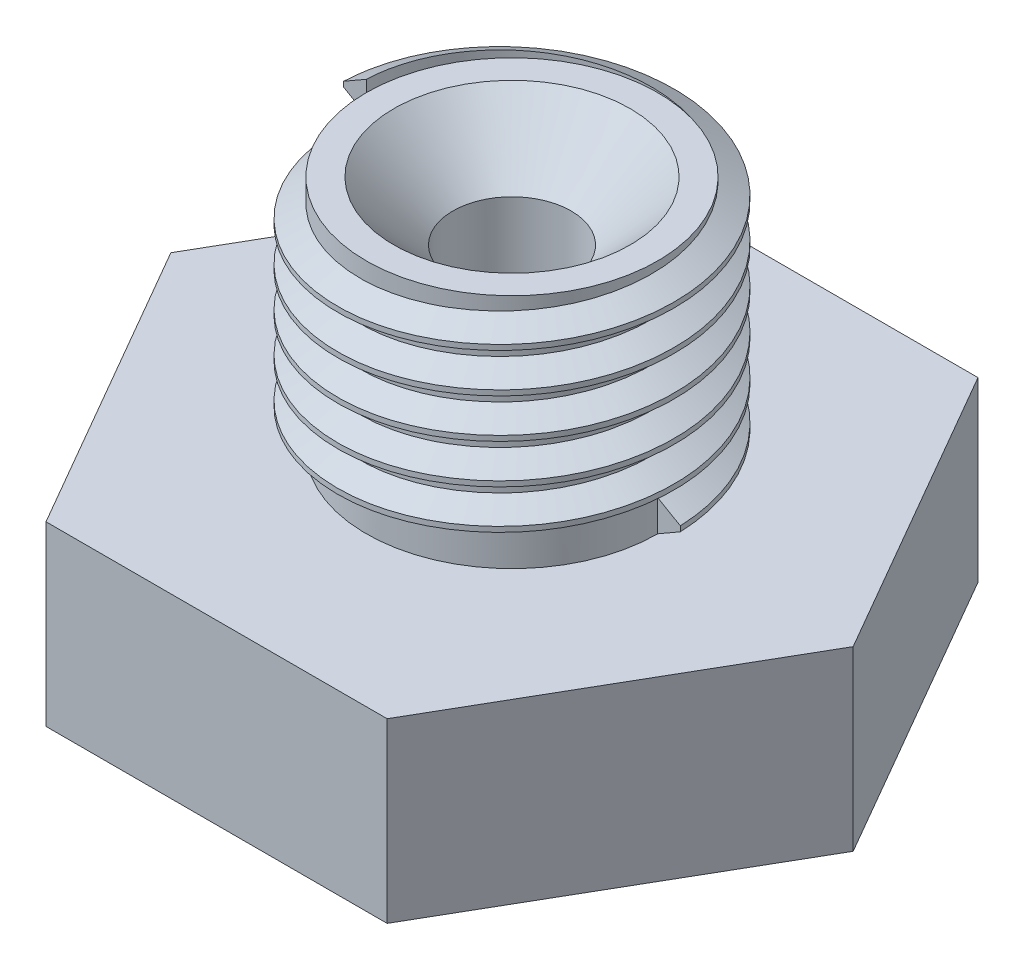
SolidWorks part; units mm, degrees
material "Polyéthylène réticulé"
ref_plane "Front" through (0, 0, 0) normal (0, 0, 1) x (1, 0, 0)
ref_plane "Top" through (0, 0, 0) normal (0, 1, 0) x (1, 0, 0)
ref_plane "Right" through (0, 0, 0) normal (1, 0, 0) x (0, 0, -1)
sketch "Esquisse1" plane through (0, 0, 0) normal (0, 0, 1) x (1, 0, 0)
  line L0 (0, 0) -> (0, 14) construction
  line L1 (0.5, 0) -> (0.5, 1.5)
  line L2 (0.5, 1.5) -> (1.5, 2.5)
  line L3 (1.5, 2.5) -> (1.5, 12.5)
  line L4 (1.5, 12.5) -> (3, 14)
  line L5 (3, 14) -> (3.7, 14)
  line L7 (3.7, 8) -> (9, 8)
  line L8 (9, 8) -> (9, 3.5)
  line L10 (3.7, 14) -> (3.7, 8)
  line L13 (9, 3.5) -> (4, 3.5)
  line L14 (4, 3.5) -> (0.5, 0)
  dimension "D1" = 14
  dimension "D2" = 7.4
  dimension "D3" = 4.5
  dimension "D4" = 3
  dimension "D5" = 135
  dimension "D6" = 1.5
  dimension "D7" = 18
  dimension "D8" = 6
  dimension "D9" = 6
  dimension "D12" = 135
  dimension "D13" = 1
revolve "Révolution1" add sketch "Esquisse1" angle 360 about L0
chamfer "Chanfrein1" [suppressed] distance 0.5 angle 45
sketch "Esquisse2" plane through (0, 8, 0) normal (0, 1, 0) x (1, 0, 0)
  line L0 (-8.6603, 0) -> (-4.3301, 7.5)
  line L1 (-4.3301, 7.5) -> (4.3301, 7.5)
  line L2 (4.3301, 7.5) -> (8.6603, 0)
  line L3 (8.6603, 0) -> (4.3301, -7.5)
  line L4 (4.3301, -7.5) -> (-4.3301, -7.5)
  line L5 (-4.3301, -7.5) -> (-8.6603, 0)
  line L6 (-6.4952, 3.75) -> (6.4952, -3.75) construction
  line L7 (6.4952, 3.75) -> (-6.4952, -3.75) construction
  circle A0 centre (0, 0) radius 9
  circle A1 centre (0, 0) radius 9 construction
  point P13 (0, 0)
  point P16 (0, 0)
  dimension "D1" = 120
  dimension "D2" = 120
  dimension "D3" = 15
extrude "Enlèv. mat.-Extru.1" cut sketch "Esquisse2" against normal through all
sketch "Esquisse3" [suppressed] plane through (0, 9, 0) normal (0, 1, 0) x (1, 0, 0)
  circle A0 centre (0, 0) radius 6.05
  circle A1 centre (0, 0) radius 8.05
  dimension "D1" = 12.1
  dimension "D2" = 2
extrude "Enlèv. mat.-Extru.2" [suppressed] cut sketch "Esquisse3" against normal blind 1.2
thread "Filetage2" pitch 1.0583 method extrude profile "Profil de filetage2" start angle 0, offset 0, length 0, pitch 1, diameter 7.4
ref_plane "Plan2" through (3.7, 8, 0) normal (0, 0, 1) x (1, 0, 0)
sketch "Profil de filetage2" plane through (3.7, 8, 0) normal (0, 0, 1) x (1, 0, 0)
  line L0 (0, 0) -> (0, 1.0583) construction
  line L1 (0, 0) -> (0.5728, 0.3307)
  line L2 (0.5728, 0.3307) -> (0.5728, 0.463)
  line L3 (0.5728, 0.463) -> (0, 0.7937)
  line L4 (0.5728, 0.3969) -> (0, 0.3969) construction
  line L11 (0, 0) -> (0, 0.7937)
  point P2 (0, 0)
  dimension "Pitch" = 1.0583
  dimension "Profile_Angle" = 60
  dimension "Profile_Land" = 0.1323
  dimension "Profile_Height" = 0.5728
